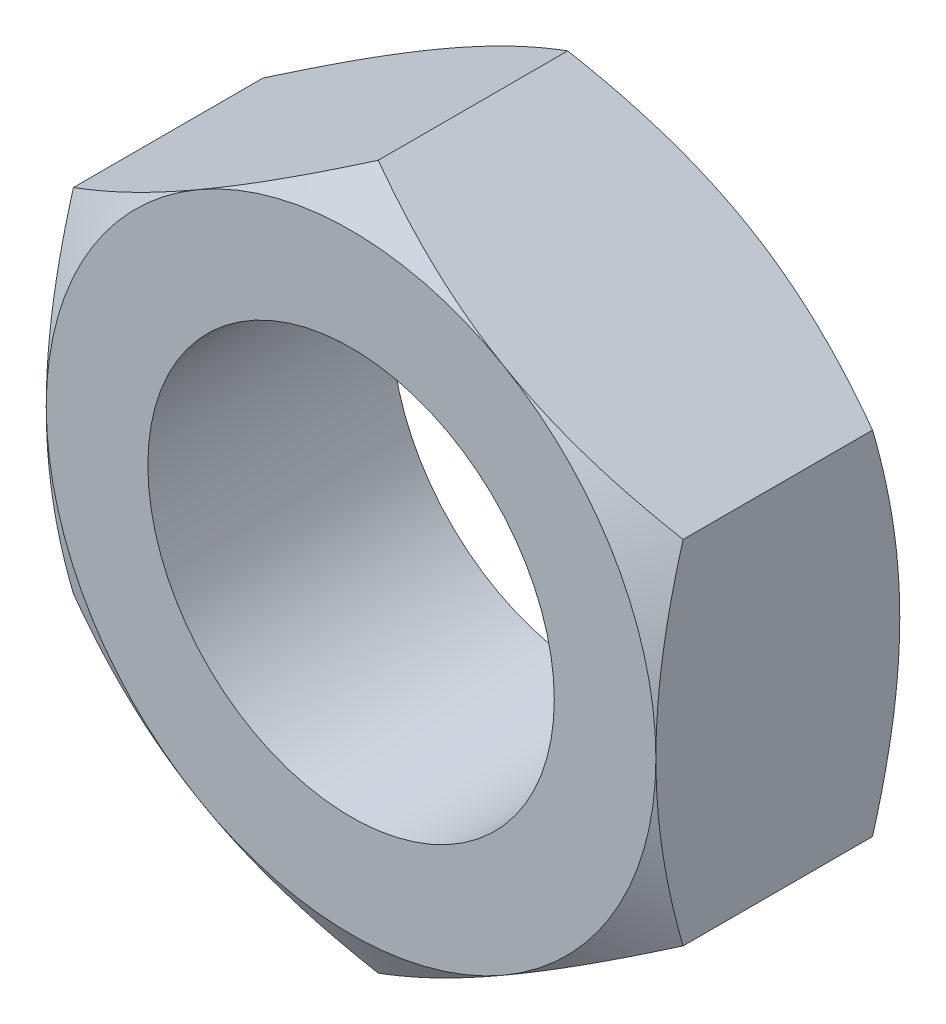
SolidWorks part; units mm, degrees
ref_plane "Plan1" through (0, 0, 0) normal (0, 0, 1) x (1, 0, 0)
ref_plane "Plan2" through (0, 0, 0) normal (0, 1, 0) x (1, 0, 0)
ref_plane "Plan3" through (0, 0, 0) normal (1, 0, 0) x (0, 0, -1)
sketch "Esquisse1" plane through (0, 0, 0) normal (0, 0, 1) x (1, 0, 0)
  line L0 (0, 0) -> (15, 0) construction
  line L1 (15, -8.6603) -> (15, 8.6603)
  line L2 (0, 0) -> (15, 8.6603) construction
  line L3 (0, 0) -> (0, 17.3205) construction
  line L4 (15, 8.6603) -> (0, 17.3205)
  line L5 (15, -8.6603) -> (0, -17.3205)
  line L6 (-15, -8.6603) -> (0, -17.3205)
  line L7 (-15, -8.6603) -> (-15, 8.6603)
  line L8 (-15, 8.6603) -> (0, 17.3205)
  circle A0 centre (0, 0) radius 15 construction
  circle A1 centre (0, 0) radius 17.3205 construction
  dimension "D2" = 30
  dimension "D1" = 30
extrude "Base-Extrusion" add sketch "Esquisse1" against normal blind 12
sketch "Esquisse2" plane through (0, 0, 0) normal (0, 1, 0) x (1, 0, 0)
  line L0 (-15, 0) -> (-26.3923, 0)
  line L1 (0, 12) -> (0, 0) construction
  line L2 (-15, 12) -> (-26.3923, 12)
  line L3 (-26.3923, 12) -> (-26.3923, 0)
  line L5 (-25.3923, 6) -> (-15, 12)
  line L6 (0, 12) -> (0, 0) construction
  line L7 (-15, 0) -> (-25.3923, 6)
  dimension "D1" = 30
  dimension "D2" = 1
  dimension "D3" = 30
revolve "Enlèvement de matière-Révolution1" cut sketch "Esquisse2" angle 360 about L6
sketch "Esquisse3" plane through (0, 0, 0) normal (0, 0, 1) x (1, 0, 0)
  circle A0 centre (0, 0) radius 10
  dimension "D1" = 20
extrude "Enlèv. mat.-Extru.1" cut sketch "Esquisse3" against normal through all
ref_axis "Axe1" through (0, 0, -50) along (0, 0, 1)
